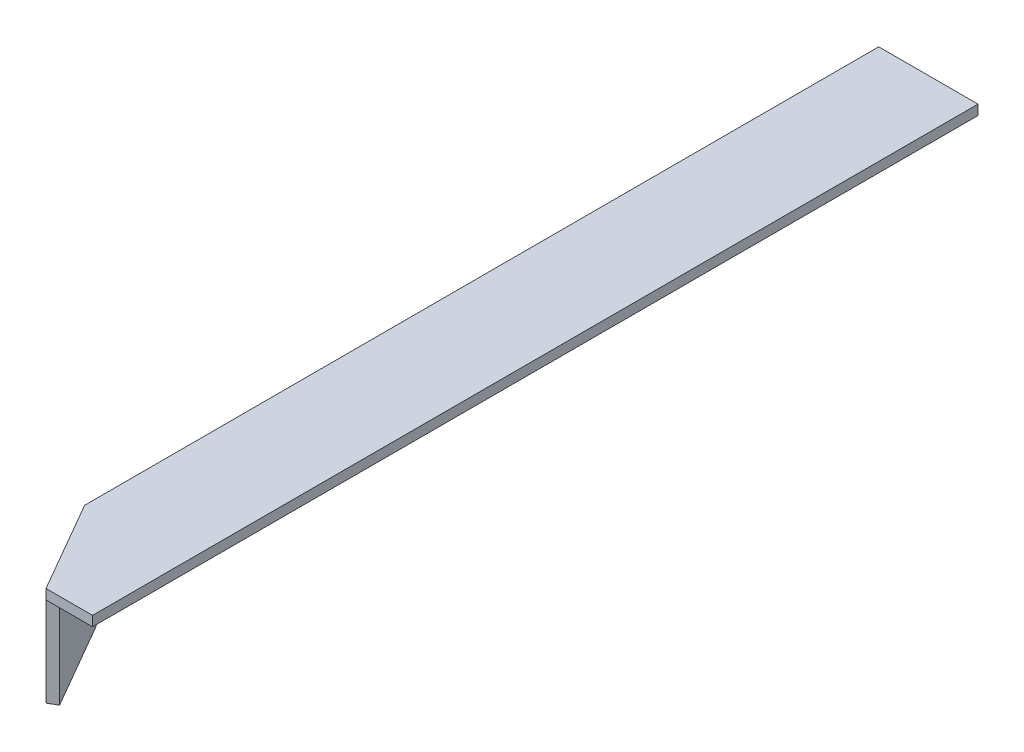
SolidWorks part; units mm, degrees
ref_plane "Front Plane" through (0, 0, 0) normal (0, 0, 1) x (1, 0, 0)
ref_plane "Top Plane" through (0, 0, 0) normal (0, 1, 0) x (1, 0, 0)
ref_plane "Right Plane" through (0, 0, 0) normal (1, 0, 0) x (0, 0, -1)
sketch "Sketch1" plane through (0, 0, 0) normal (0, 0, 1) x (1, 0, 0)
  line L0 (-8, 8) -> (72, 8)
  line L1 (72, 8) -> (72, 0)
  line L2 (72, 0) -> (0, 0)
  line L3 (0, 0) -> (0, -72)
  line L4 (0, -72) -> (-8, -72)
  line L5 (-8, -72) -> (-8, 8)
  dimension "D1" = 80
  dimension "D2" = 80
  dimension "D3" = 8
  dimension "D4" = 8
extrude "Boss-Extrude1" add sketch "Sketch1" along normal blind 640
sketch "Sketch3" plane through (0, 0, 0) normal (0, 1, 0) x (1, 0, 0)
  line L0 (-8, -640) -> (34.5, -713.6122)
  line L1 (34.5, -713.6122) -> (72, -713.6122)
  line L2 (72, -713.6122) -> (72, -640)
  line L3 (72, -640) -> (-8, -640)
  line L4 (-8, -640) -> (-8, 0) construction
  dimension "D1" = 210
  dimension "D2" = 85
extrude "Boss-Extrude2" add sketch "Sketch3" along normal blind 8
sketch "Sketch4" plane through (0, 0, 0) normal (0, -1, 0) x (1, 0, 0)
  line L0 (-8, 640) -> (34.5, 713.6122)
  line L1 (34.5, 713.6122) -> (41.4282, 709.6122)
  line L2 (41.4282, 709.6122) -> (1.2376, 640)
  line L3 (-8, 640) -> (0, 640) construction
  line L4 (1.2376, 640) -> (-8, 640)
  dimension "D1" = 8
extrude "Boss-Extrude3" add sketch "Sketch4" along normal blind 72
